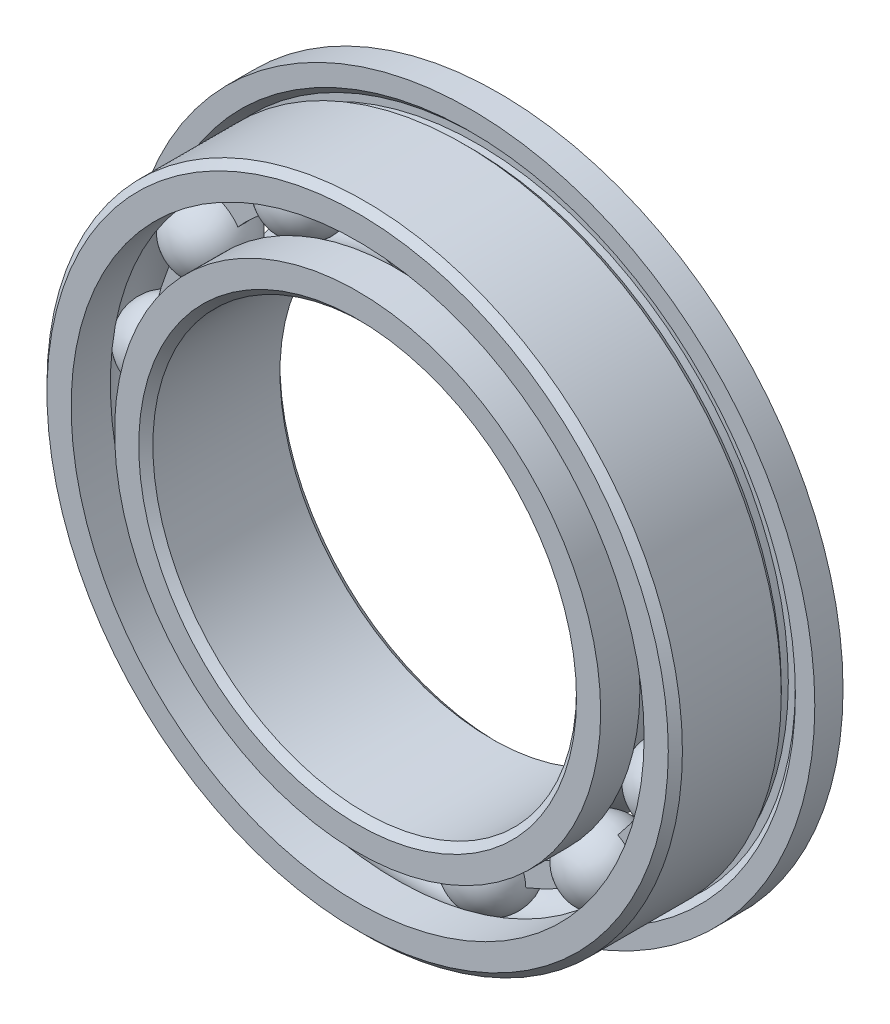
SolidWorks part; units mm, degrees
ref_plane "Front Plane" through (0, 0, 0) normal (0, 0, 1) x (1, 0, 0)
ref_plane "Top Plane" through (0, 0, 0) normal (0, 1, 0) x (1, 0, 0)
ref_plane "Right Plane" through (0, 0, 0) normal (1, 0, 0) x (0, 0, -1)
sketch "Sketch1" plane through (0, 0, 0) normal (1, 0, 0) x (0, 0, -1)
  line L0 (-2, 0) -> (2, 0) construction
  line L1 (0, 9) -> (0, -9) construction
  line L2 (1.8, 9) -> (-1.8, 9) construction
  line L3 (-1.8, 9) -> (-2, 8.8)
  line L4 (-2, 8.8) -> (-2, 8.1154)
  line L5 (-2, 8.1154) -> (-0.8889, 8.1154)
  line L6 (2, 8.1154) -> (0.8889, 8.1154)
  line L7 (2, 8.8) -> (2, 8.1154)
  line L8 (1.8, 9) -> (2, 8.8) construction
  line L9 (0, 9) -> (0, 7.5) construction
  line L10 (0, 7.5) -> (0, 6) construction
  line L11 (1.2, 0) -> (1.2, 9) construction
  line L12 (2, 8.8) -> (2, 9.75)
  line L13 (2, 9.75) -> (1.2, 9.75)
  line L14 (1.2, 9.75) -> (1.2, 9.2)
  line L15 (1.2, 9.2) -> (1.4, 9)
  line L16 (1.4, 9) -> (1.4, 8.8)
  line L17 (1.4, 8.8) -> (1.2, 8.8)
  line L18 (1.2, 8.8) -> (1, 9)
  line L19 (-1.8, 9) -> (1, 9)
  line L20 (2, 9.75) -> (2, -9.75) construction
  line L21 (1.2, 9) -> (1.2, 9.2) construction
  line L22 (1.2, 9) -> (1, 9) construction
  arc A0 (-0.8889, 8.1154) -> (0.8889, 8.1154) centre (0, 7.5) cw
  point P14 (0, 6)
  point P15 (1.2, 0)
  point P25 (2, 0)
  dimension "Width" = 4
  dimension "OD" = 18
  dimension "D1" = 45
  dimension "D2" = 0.2
  dimension "ID" = 12
  dimension "D3" = 1.7778
  dimension "D4" = 0.6154
  dimension "Th" = 0.8
  dimension "Flange OD" = 19.5
revolve "Revolve1" add sketch "Sketch1" angle 360 about L0
sketch "Sketch3" plane through (0, 0, 0) normal (1, 0, 0) x (0, 0, -1)
  line L0 (-2, 6.8846) -> (-0.8889, 6.8846)
  line L1 (0, 9) -> (0, -9) construction
  line L2 (-2, 8.8) -> (-2, 8.1154) construction
  line L3 (-2, 6.8846) -> (-2, 6.2)
  line L4 (-1.8, 9) -> (-2, 8.8) construction
  line L5 (-2, 6.2) -> (-1.8, 6)
  line L6 (-1.8, 6) -> (1.8, 6)
  line L8 (1.8, 6) -> (2, 6.2)
  line L10 (2, 6.2) -> (2, 6.8846)
  line L11 (2, 6.8846) -> (0.8889, 6.8846)
  line L13 (1.8, 9) -> (2, 8.8) construction
  arc A0 (0.8889, 8.1154) -> (-0.8889, 8.1154) centre (0, 7.5) ccw construction
  arc A1 (0.8889, 6.8846) -> (-0.8889, 6.8846) centre (0, 7.5) cw
revolve "Revolve3" add sketch "Sketch3" angle 360 about L0
sketch "Sketch6" plane through (0, 0, 0) normal (1, 0, 0) x (0, 0, -1)
  line L1 (-0.1026, 7.8077) -> (0.1026, 7.8077)
  line L2 (-0.1026, 7.8077) -> (-0.1026, 7.1923)
  line L3 (-0.1026, 7.1923) -> (0.1026, 7.1923)
  line L4 (0.1026, 7.8077) -> (0.1026, 7.1923)
  line L5 (-0.1026, 7.8077) -> (0.1026, 7.1923) construction
  line L6 (-0.1026, 7.1923) -> (0.1026, 7.8077) construction
  point P4 (0, 7.5)
  dimension "D1" = 0.6154
  dimension "D2" = 0.2051
revolve "Revolve6" add sketch "Sketch6" angle 360 about L0
sketch "Sketch4" plane through (0, 0, 0) normal (1, 0, 0) x (0, 0, -1)
  line L0 (-1.0811, 7.5) -> (1.0811, 7.5)
  arc A2 (-1.0811, 7.5) -> (1.0811, 7.5) centre (0, 7.5) cw
  arc A3 (0.8889, 8.1154) -> (-0.8889, 8.1154) centre (0, 7.5) ccw construction
revolve "Revolve4" add sketch "Sketch4" angle 360 about L0
ref_axis "Axis1" through (0, 0, -2) along (0, 0, 1)
pattern_circular "CirPattern1" count 13 every 27.692 about axis through (0, 0, -2) along (0, 0, 1) of bodies 104
sketch "Sketch5" plane through (0, 0, 0) normal (1, 0, 0) x (0, 0, -1)
  line L0 (-2, 8.1154) -> (-0.8889, 8.1154) construction
  line L1 (-1.9, 8.1154) -> (-1.0811, 8.1154)
  line L2 (-1.9, 8.1154) -> (-1.9, 6.8846)
  line L3 (-1.9, 6.8846) -> (-1.0811, 6.8846)
  line L4 (-1.0811, 8.1154) -> (-1.0811, 6.8846)
  line L5 (-2, 6.8846) -> (-0.8889, 6.8846) construction
  line L6 (2, 8.1154) -> (0.8889, 8.1154) construction
  line L7 (1.9, 8.1154) -> (1.0811, 8.1154)
  line L8 (1.9, 8.1154) -> (1.9, 6.8846)
  line L9 (1.9, 6.8846) -> (1.0811, 6.8846)
  line L10 (1.0811, 8.1154) -> (1.0811, 6.8846)
  line L11 (2, 6.8846) -> (0.8889, 6.8846) construction
  line L12 (-1.8, 9) -> (-2, 8.8) construction
  point P18 (-1.9, 8.9)
revolve "Revolve5" [suppressed] add sketch "Sketch5" angle 360 about L0
ref_axis "Center Axis 1" through (0, 0, -1.8) along (0, 0, 1)
ref_plane "Contact Plane 1" through (0, 0, -2) normal (0, 0, -1) x (-1, 0, 0)
ref_plane "Contact Plane 2" through (0, 0, -1.2) normal (0, 0, 1) x (1, 0, 0)
equation "\"D2@Sketch1\" = \"Width@Sketch1\"*.05"
equation "\"D3@Sketch1\" = \"Width@Sketch1\"/2.25"
equation "\"D4@Sketch1\" = (((\"OD@Sketch1\"-\"Width@Sketch1\")/2)/3.25)/3.5"
equation "\"D2@CirPattern1\" = 360/\"Balls@CirPattern1\""
equation "\"D1@Sketch6\"=\"D4@Sketch1\""
equation "\"D2@Sketch6\"=\"D1@Sketch6\"/3"
